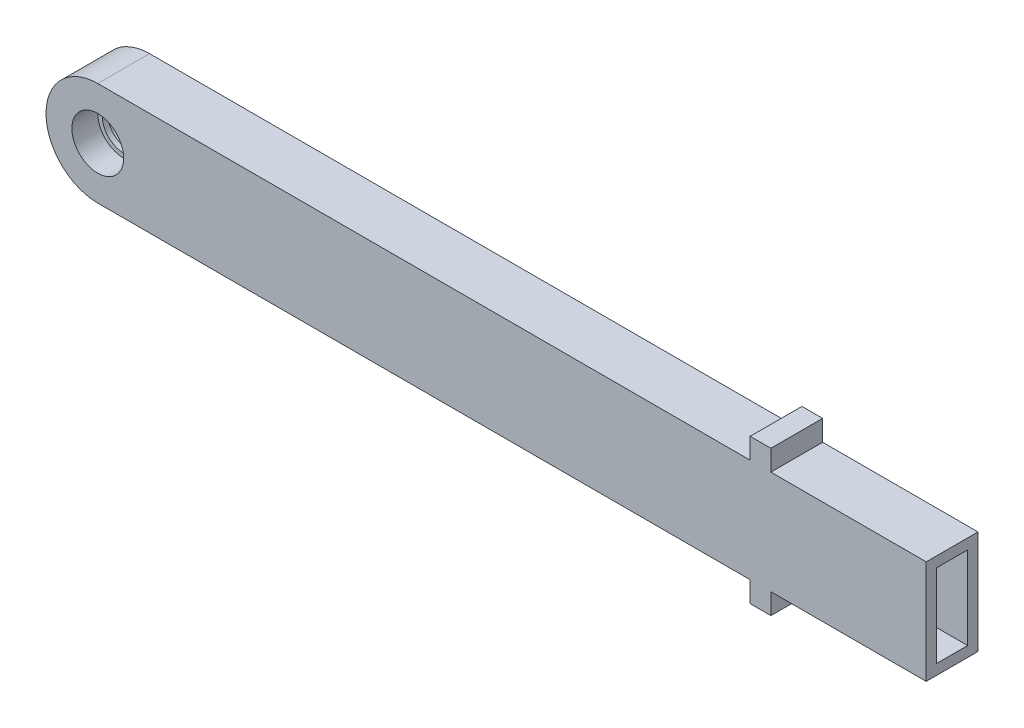
SolidWorks part; units mm, degrees
ref_plane "Front Plane" through (0, 0, 0) normal (0, 0, 1) x (1, 0, 0)
ref_plane "Top Plane" through (0, 0, 0) normal (0, 1, 0) x (1, 0, 0)
ref_plane "Right Plane" through (0, 0, 0) normal (1, 0, 0) x (0, 0, -1)
sketch "Sketch1" plane through (0, 0, 0) normal (0, 0, 1) x (1, 0, 0)
  line L0 (0, 0) -> (80, 0)
  line L1 (0, 0) -> (80, 0) construction
  line L2 (0, 5) -> (80, 5)
  line L3 (0, -5) -> (80, -5)
  line L4 (80, 5) -> (80, -5)
  circle A0 centre (0, 0) radius 2.5
  circle A1 centre (1.2272, 0) radius 0.1309
  arc A2 (0, 5) -> (0, -5) centre (0, 0) ccw
  point P6 (40, 0)
  dimension "D1" = 5
  dimension "D2" = 80
  dimension "D3" = 10
extrude "Boss-Extrude1" add sketch "Sketch1" along normal blind 5 contours L2 A2 L3 L4 A0 region at (79.1441, -2.5, 0)
sketch "Sketch2" plane through (80, 0, 0) normal (1, 0, 0) x (0, 0, -1)
  line L0 (-5, 5) -> (0, 5) construction
  line L1 (-4, 4) -> (-1, 4)
  line L2 (-4, 4) -> (-4, -4)
  line L3 (-4, -4) -> (-1, -4)
  line L4 (-1, 4) -> (-1, -4)
  line L5 (-5, 5) -> (-5, -5) construction
  line L6 (0, 5) -> (0, -5) construction
  line L7 (-5, -5) -> (0, -5) construction
  dimension "D1" = 1
  dimension "D2" = 1
  dimension "D3" = 1
  dimension "D4" = 1
extrude "Cut-Extrude1" cut sketch "Sketch2" against normal blind 10
sketch "Sketch3" plane through (0, 0, 0) normal (0, 0, -1) x (-1, 0, 0)
  line L0 (0, 0) -> (-20, 0) construction
  line L1 (-20, 1.5091) -> (0, 2.5)
  line L2 (-20, -1.5091) -> (0, -2.5)
  arc A0 (-20, 1.5091) -> (-20, -1.5091) centre (-20, 0) ccw
  circle A1 centre (0, 0) radius 2.5 construction
  arc A3 (0, -2.5) -> (0, 2.5) centre (0, 0) ccw
  dimension "D1" = 20
extrude "Cut-Extrude2" cut sketch "Sketch3" against normal blind 2
sketch "Sketch4" plane through (0, 0, 2) normal (0, 0, -1) x (-1, 0, 0)
  circle A0 centre (0, 0) radius 2.0726
  circle A1 centre (0, 0) radius 2.5
extrude "Boss-Extrude2" add sketch "Sketch4" against normal blind 0.5
sketch "Sketch5" plane through (0, 5, 0) normal (0, 1, 0) x (1, 0, 0)
  line L0 (65, 0) -> (65, -5)
  line L1 (0, 0) -> (80, 0) construction
  line L2 (0, -5) -> (80, -5) construction
  line L3 (80, -5) -> (80, 0) construction
  line L4 (63, 0) -> (63, -5)
  line L5 (63, -5) -> (65, -5)
  line L6 (63, 0) -> (65, 0)
  dimension "D1" = 15
  dimension "D2" = 2
extrude "Boss-Extrude3" add sketch "Sketch5" along normal blind 2
extrude "Boss-Extrude4" add sketch "Sketch5<2>" against normal blind 12
sketch "Sketch5<2>" plane through (0, 5, 0) normal (0, 1, 0) x (1, 0, 0) same geometry as "Sketch5"
